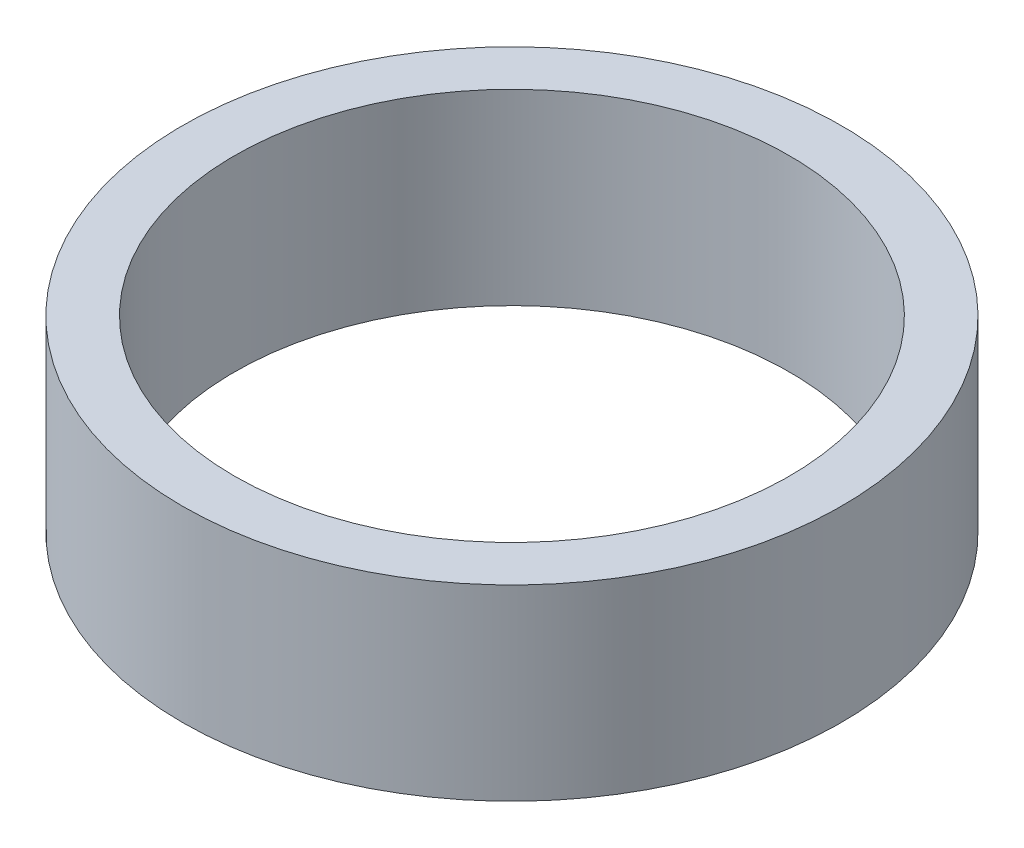
SolidWorks part; units mm, degrees
ref_plane "Front Plane" through (0, 0, 0) normal (0, 0, 1) x (1, 0, 0)
ref_plane "Top Plane" through (0, 0, 0) normal (0, 1, 0) x (1, 0, 0)
ref_plane "Right Plane" through (0, 0, 0) normal (1, 0, 0) x (0, 0, -1)
sketch "Sketch1" plane through (0, 0, 0) normal (0, 1, 0) x (1, 0, 0)
  circle A0 centre (0, 0) radius 47.5
  dimension "FLANGE_OD" = 95
extrude "Boss-Extrude1" add sketch "Sketch1" along normal blind 27
sketch "Sketch2" plane through (0, 0, 0) normal (0, 1, 0) x (1, 0, 0)
  circle A0 centre (0, 0) radius 40
  dimension "BORE_D" = 80
extrude "Cut-Extrude1" cut sketch "Sketch2" along normal through all
sketch "Sketch3" plane through (0, 27, 0) normal (0, 1, 0) x (1, 0, 0)
  circle A0 centre (0, 0) radius 21.6762 construction
  circle A1 centre (-21.6762, 0) radius 1.5
  dimension "BOLT_D" = 3
  dimension "BOLT_PCD" = 43.3524
extrude "Cut-Extrude2" cut sketch "Sketch3" against normal blind 16.4689 rebuild error yes
pattern_circular "CirPattern1" count 6 over 360 rebuild error yes
